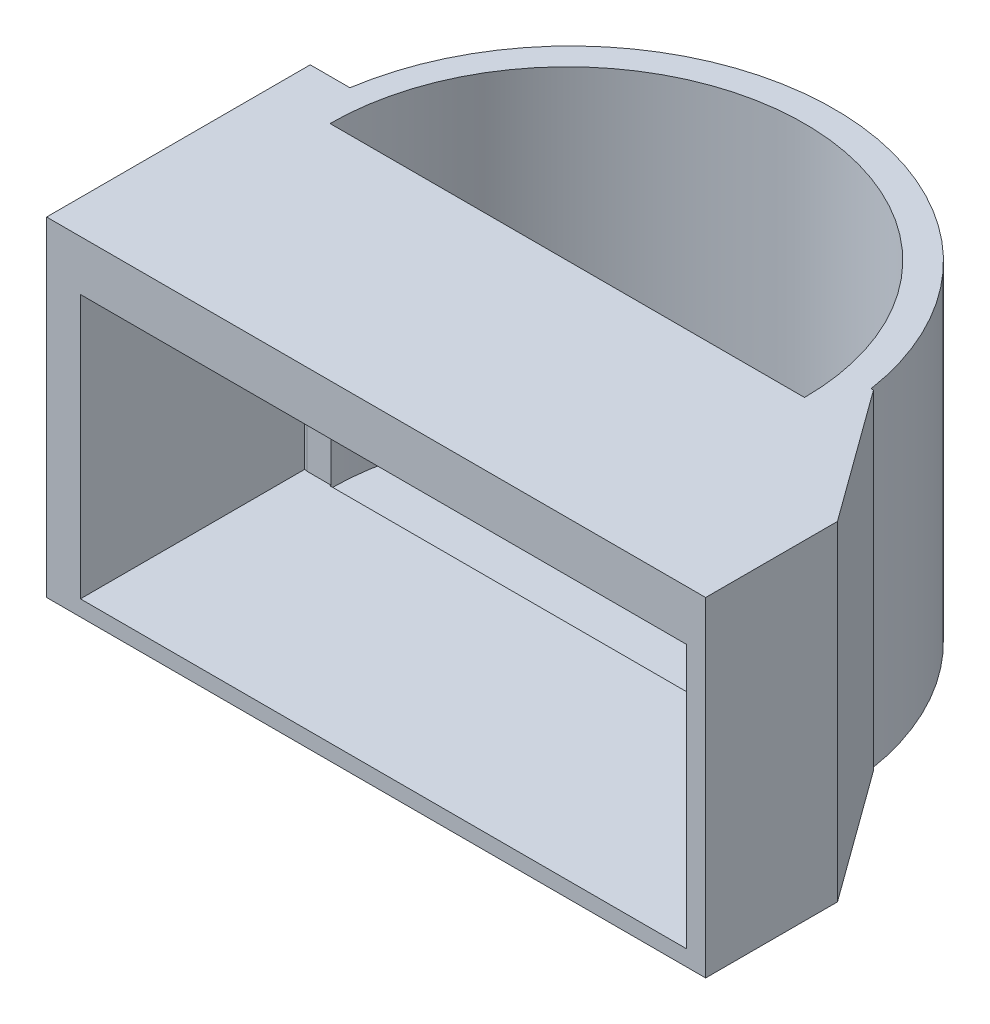
SolidWorks part; units mm, degrees
material "ABS"
ref_plane "Alzado" through (0, 0, 0) normal (0, 0, 1) x (1, 0, 0)
ref_plane "Planta" through (0, 0, 0) normal (0, 1, 0) x (1, 0, 0)
ref_plane "Vista lateral" through (0, 0, 0) normal (1, 0, 0) x (0, 0, -1)
sketch "Croquis1" plane through (0, 0, 0) normal (0, 1, 0) x (1, 0, 0)
  line L1 (-25, -10) -> (25, -10)
  line L2 (-25, -10) -> (-25, 10)
  line L3 (-25, 10) -> (25, 10)
  line L4 (25, -10) -> (25, 10)
  line L5 (-25, -10) -> (25, 10) construction
  line L6 (-25, 10) -> (25, -10) construction
  point P0 (0, 0)
  dimension "D1" = 50
  dimension "D2" = 20
extrude "Saliente-Extruir1" add sketch "Croquis1" along normal blind 25
sketch "Croquis5" plane through (0, 2.5662, 10) normal (0, 0, 1) x (1, 0, 0)
  line L1 (23.565, 18.6274) -> (-22.435, 18.6274)
  line L2 (23.565, 18.6274) -> (23.565, -1.3726)
  line L3 (23.565, -1.3726) -> (-22.435, -1.3726)
  line L4 (-22.435, 18.6274) -> (-22.435, -1.3726)
  line L5 (23.565, 18.6274) -> (-22.435, -1.3726) construction
  line L6 (23.565, -1.3726) -> (-22.435, 18.6274) construction
  point P0 (0.565, 8.6274)
  dimension "D1" = 46
  dimension "D2" = 20
extrude "Cortar-Extruir1" cut sketch "Croquis5" against normal blind 17
sketch "Croquis6" plane through (0, 0, 0) normal (0, -1, 0) x (1, 0, 0)
  line L0 (-22.217, -6.9763) -> (17.783, -6.9763)
  arc A0 (-22.217, -6.9763) -> (17.783, -6.9763) centre (-2.217, -6.9763) ccw
  dimension "D1" = 20
extrude "Saliente-Extruir2" add sketch "Croquis6" against normal blind 25
sketch "Croquis11" plane through (0, 25, 0) normal (0, 1, 0) x (1, 0, 0)
  line L0 (-20.3919, 6.8929) -> (15.6081, 6.8929)
  arc A0 (-20.3919, 6.8929) -> (15.6081, 6.8929) centre (-2.3919, 6.8929) cw
  dimension "D1" = 18
  dimension "D2" = 36
extrude "Cortar-Extruir5" cut sketch "Croquis11" against normal blind 24
chamfer "Chaflán2" distance 10 angle 36 2 edges at (25, 12.5, -10) (23.565, 11.1936, -7) first distance on face at (25, 12.5, 0) first distance on face at (23.565, 11.1936, 1.5)
